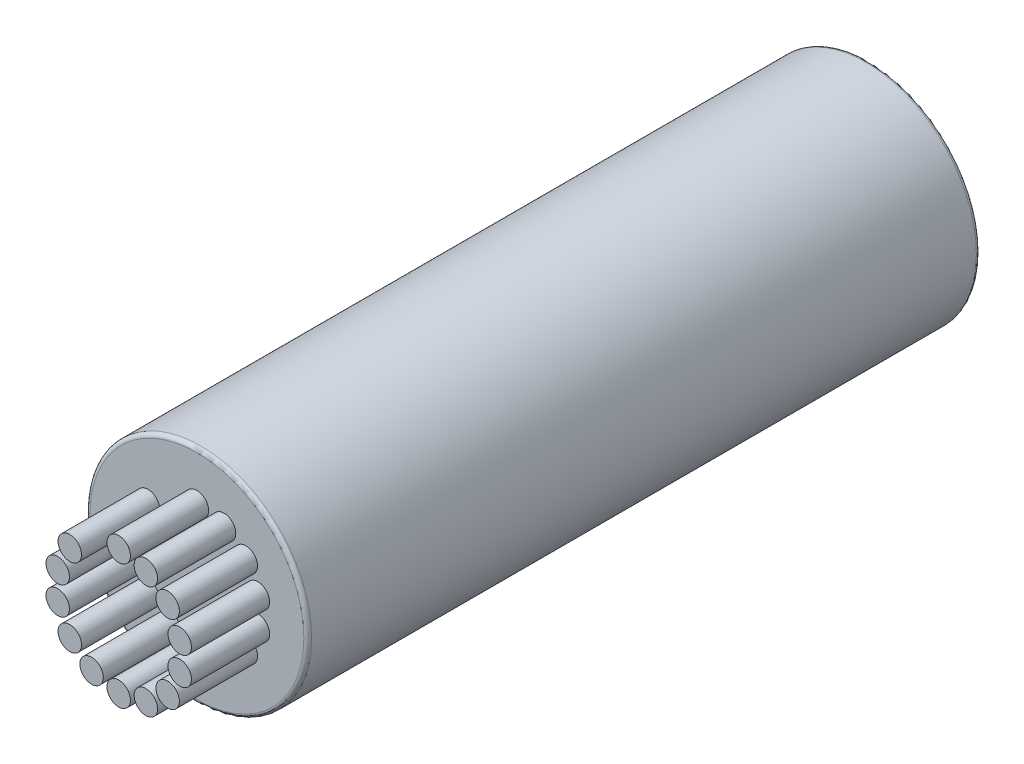
SolidWorks part; units mm, degrees
ref_plane "Front Plane" through (0, 0, 0) normal (0, 0, 1) x (1, 0, 0)
ref_plane "Top Plane" through (0, 0, 0) normal (0, 1, 0) x (1, 0, 0)
ref_plane "Right Plane" through (0, 0, 0) normal (1, 0, 0) x (0, 0, -1)
sketch "Sketch1" plane through (0, 0, 0) normal (0, 0, 1) x (1, 0, 0)
  circle A0 centre (0, 0) radius 7.0865
  dimension "D1" = 14.173
extrude "Boss-Extrude1" add sketch "Sketch1" along normal blind 43
sketch "Sketch2" plane through (0, 0, 0) normal (0, 0, -1) x (-1, 0, 0)
  circle A0 centre (0, 0) radius 5
  dimension "D1" = 10
extrude "Cut-Extrude1" cut sketch "Sketch2" against normal blind 0.1
sketch "Sketch3" plane through (0, 0, 43) normal (0, 0, 1) x (1, 0, 0)
  circle A13 centre (0, 4) radius 0.75
  circle A14 centre (1.7355, 3.6039) radius 0.75
  circle A15 centre (3.1273, 2.494) radius 0.75
  circle A16 centre (3.8997, 0.8901) radius 0.75
  circle A17 centre (3.8997, -0.8901) radius 0.75
  circle A18 centre (3.1273, -2.494) radius 0.75
  circle A19 centre (1.7355, -3.6039) radius 0.75
  circle A20 centre (0, -4) radius 0.75
  circle A21 centre (-1.7355, -3.6039) radius 0.75
  circle A22 centre (-3.1273, -2.494) radius 0.75
  circle A23 centre (-3.8997, -0.8901) radius 0.75
  circle A49 centre (-3.8997, 0.8901) radius 0.75
  circle A50 centre (-3.1273, 2.494) radius 0.75
  circle A52 centre (-1.7355, 3.6039) radius 0.75 [skipped]
  point P30 (0, 0)
  point P54 (0, 0)
  dimension "D3" = 14
  dimension "D2" = 1.5
  dimension "D1" = 4
extrude "Boss-Extrude2" add sketch "Sketch3" along normal blind 5
fillet "Fillet1" radius 0.25 2 edges at (7.0865, 0, 43) (7.0865, 0, 0)
